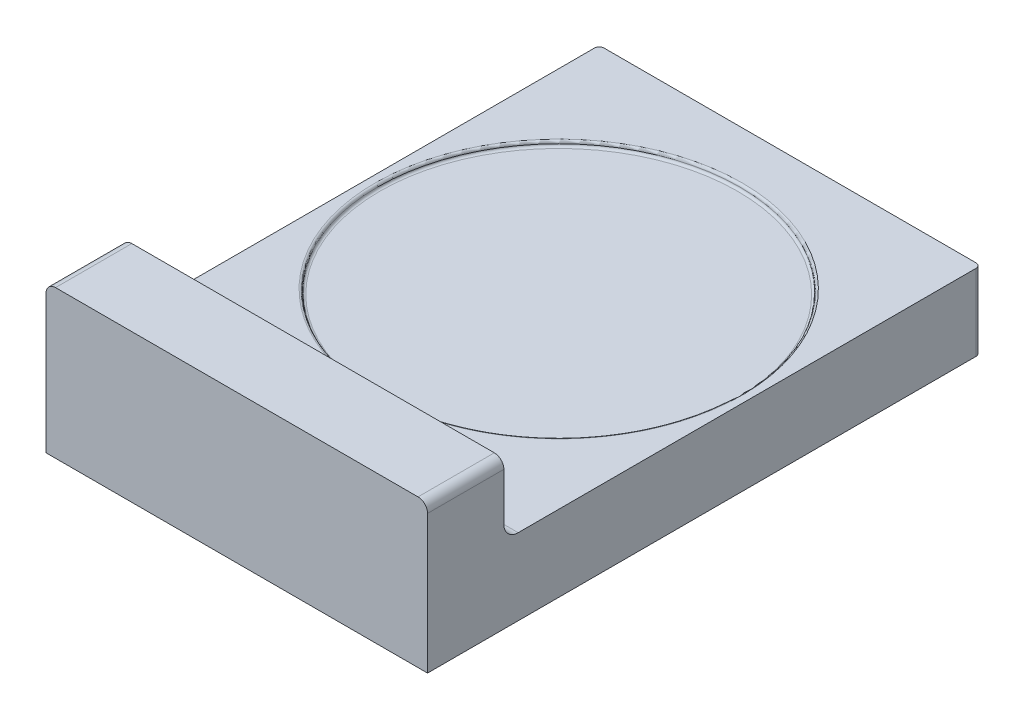
SolidWorks part; units mm, degrees
ref_plane "Front Plane" through (0, 0, 0) normal (0, 0, 1) x (1, 0, 0)
ref_plane "Top Plane" through (0, 0, 0) normal (0, 1, 0) x (1, 0, 0)
ref_plane "Right Plane" through (0, 0, 0) normal (1, 0, 0) x (0, 0, -1)
sketch "Sketch1" plane through (0, 0, 0) normal (1, 0, 0) x (0, 0, -1)
  line L8 (0, 0) -> (580, 0)
  line L9 (0, 0) -> (0, 80)
  line L10 (0, 80) -> (580, 80)
  line L11 (580, 0) -> (580, 80)
  dimension "D1" = 580
  dimension "D2" = 80
extrude "Boss-Extrude1" add sketch "Sketch1" along normal blind 400
sketch "Sketch2" plane through (0, 80, 0) normal (0, 1, 0) x (1, 0, 0)
  line L0 (400, 580) -> (400, 0) construction
  line L1 (0, 0) -> (400, 0)
  line L2 (0, 0) -> (0, 80)
  line L3 (0, 80) -> (400, 80)
  line L4 (400, 0) -> (400, 80)
  dimension "D1" = 80
extrude "Boss-Extrude2" add sketch "Sketch2" along normal blind 75
fillet "Fillet2" radius 10 2 edges at (0, 155, -40) (400, 155, -40)
fillet "Fillet3" radius 5 2 edges at (0, 40, -580) (400, 40, -580)
fillet "Fillet4" radius 15 1 edges at (200, 80, -80)
sketch "Sketch3" plane through (0, 80, 0) normal (0, 1, 0) x (1, 0, 0)
  line L8 (200, 580) -> (200, 95) construction
  line L9 (395, 580) -> (5, 580) construction
  line L10 (0, 95) -> (400, 95) construction
  circle A1 centre (200, 337.5) radius 190
  point P2 (200, 337.5)
  dimension "D1" = 380
extrude "Cut-Extrude1" cut sketch "Sketch3" against normal blind 5
fillet "Fillet6" radius 2.5 2 edges at (200, 75, -147.5) (200, 80, -147.5)
